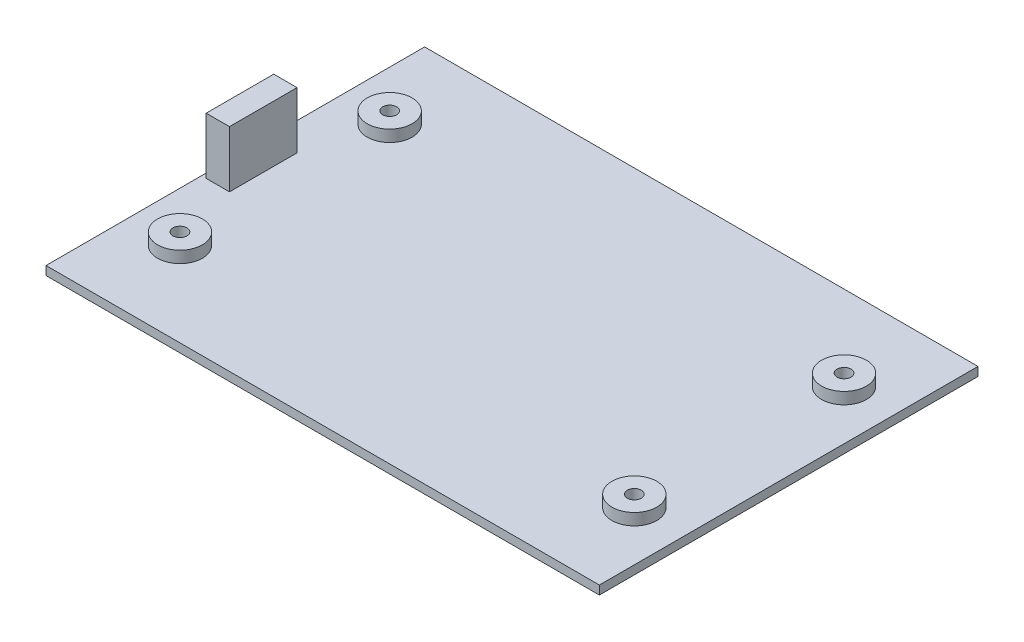
SolidWorks part; units mm, degrees
material "PLA"
ref_plane "前视基准面" through (0, 0, 0) normal (0, 0, 1) x (1, 0, 0)
ref_plane "上视基准面" through (0, 0, 0) normal (0, 1, 0) x (1, 0, 0)
ref_plane "右视基准面" through (0, 0, 0) normal (1, 0, 0) x (0, 0, -1)
other "Configuration Table"
sketch "草图1" plane through (0, 0, 0) normal (0, 1, 0) x (1, 0, 0)
  line L1 (-47.5, 32.5) -> (47.5, 32.5)
  line L2 (-47.5, 32.5) -> (-47.5, -32.5)
  line L3 (-47.5, -32.5) -> (47.5, -32.5)
  line L4 (47.5, 32.5) -> (47.5, -32.5)
  line L5 (-47.5, 32.5) -> (47.5, -32.5) construction
  line L6 (-47.5, -32.5) -> (47.5, 32.5) construction
  point P0 (0, 0)
  dimension "D1" = 65
  dimension "D2" = 95
extrude "凸台-拉伸1" add sketch "草图1" along normal blind 1.5
sketch "草图2" plane through (0, 0, 0) normal (0, -1, 0) x (1, 0, 0)
  circle A0 centre (-39, -18) radius 6
  circle A1 centre (-39, 18) radius 6
  circle A2 centre (39, -18) radius 6
  circle A3 centre (39, 18) radius 6
  dimension "D1" = 12
  dimension "D2" = 12
  dimension "D3" = 12
  dimension "D4" = 12
extrude "切除-拉伸1" cut sketch "草图2" against normal blind 0.75
sketch "草图7" plane through (0, 1.5, 0) normal (0, 1, 0) x (1, 0, 0)
  line L0 (-55, 0) -> (55, 0) construction
  line L1 (0, -55) -> (0, 55) construction
  circle A0 centre (39, 18) radius 1.2
  circle A1 centre (39, 18) radius 3.85
  circle A2 centre (39, -18) radius 3.85
  circle A3 centre (39, -18) radius 1.2
  circle A4 centre (-39, -18) radius 1.2
  circle A5 centre (-39, -18) radius 3.85
  circle A6 centre (-39, 18) radius 3.85
  circle A7 centre (-39, 18) radius 1.2
  dimension "D1" = 2.4
  dimension "D2" = 7.7
extrude "凸台-拉伸3" add sketch "草图7" along normal blind 2
hole_wizard "ST2.2 十字槽沉头自攻螺钉的锥形沉头孔1" positions "3D草图1" profile "草图8" countersink size "ST2.2" standard "GB" end condition through all
sketch3d "3D草图1"
  line L0 (-39, 0.75, 18) -> (-39, 0, 18) construction
  line L1 (-39, 0.75, -18) -> (-39, 0, -18) construction
  line L2 (39, 0.75, -18) -> (39, 0, -18) construction
  line L3 (39, 0.75, 18) -> (39, 0, 18) construction
  point P0 (-39, 0, 18)
  point P4 (-39, 0, -18)
  point P8 (39, 0, -18)
  point P12 (39, 0, 18)
sketch "草图8" plane through (-39, 0, 18) normal (1, 0, 0) x (0, 0, -1)
  line L0 (0, 0) -> (0, 3.5)
  line L1 (0, 3.5) -> (1.2, 3.5)
  line L2 (1.2, 3.5) -> (1.2, 1)
  line L3 (1.2, 1) -> (2.2, 0)
  line L5 (2.2, 0) -> (0, 0)
  line L6 (-1.2, 1) -> (-2.2, 0) construction
  line L11 (0, -6.35) -> (0, 107.95) construction
  dimension "通孔孔直径" = 2.4
  dimension "通孔孔深度" = 3.5
  dimension "近端锥形沉头孔直径" = 4.4
  dimension "近端锥形沉头孔角度" = 90
sketch "草图11" plane through (0, 0, 0) normal (0, -1, 0) x (1, 0, 0)
  line L0 (-53.5, -5.8) -> (-39.7, -5.8) construction
  line L1 (-42.7, -5.8) -> (-46.7, -5.8)
  line L2 (-42.7, -5.8) -> (-42.7, 5.8)
  line L3 (-42.7, 5.8) -> (-46.7, 5.8)
  line L4 (-46.7, -5.8) -> (-46.7, 5.8)
  line L5 (-39.7, 5.8) -> (-53.5, 5.8) construction
  line L6 (-46.8, 4.5) -> (-46.8, -4.5) construction
  dimension "D1" = 0.1
  dimension "D2" = 4
extrude "充电板档板凸台-拉伸5" add sketch "草图11" against normal up to surface (11.2 mm away)
